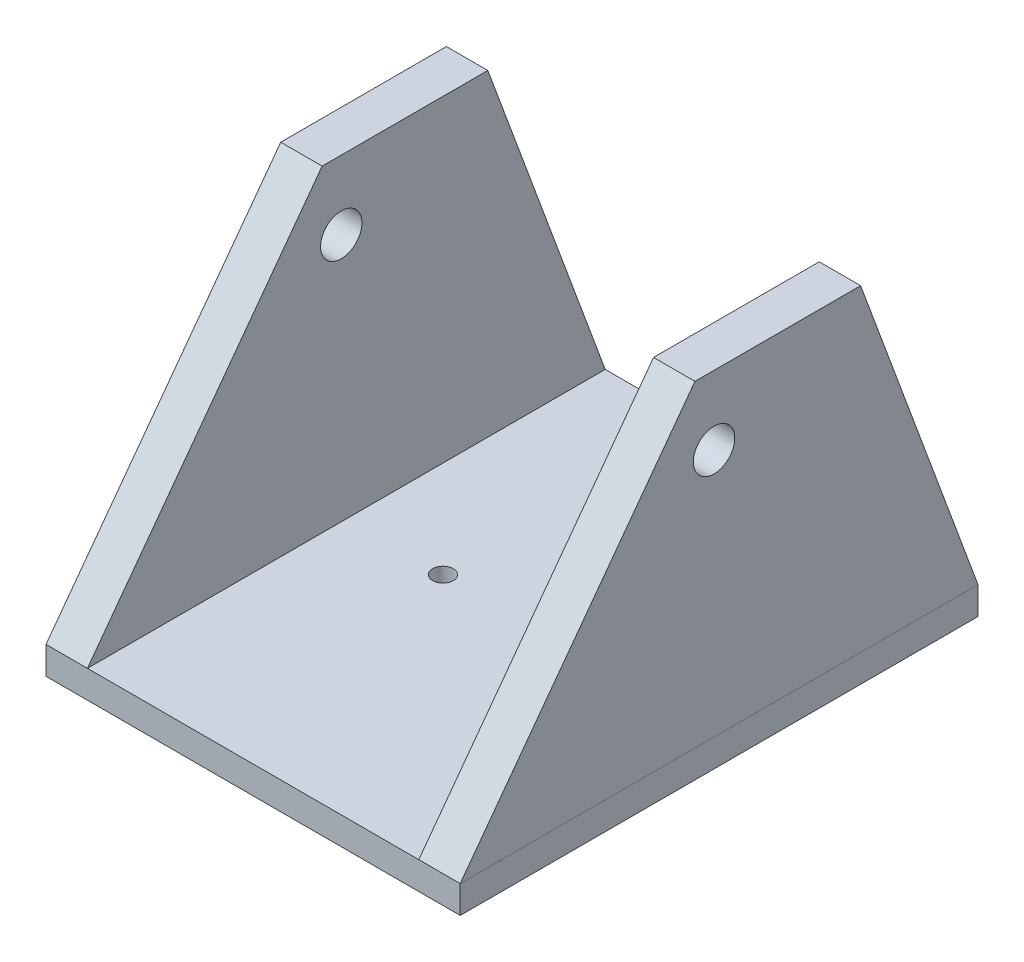
SolidWorks part; units mm, degrees
ref_plane "Front Plane" through (0, 0, 0) normal (0, 0, 1) x (1, 0, 0)
ref_plane "Top Plane" through (0, 0, 0) normal (0, 1, 0) x (1, 0, 0)
ref_plane "Right Plane" through (0, 0, 0) normal (1, 0, 0) x (0, 0, -1)
sketch "Sketch1" plane through (0, 0, 0) normal (0, 1, 0) x (1, 0, 0)
  line L0 (30, 0) -> (-30, 0)
  line L1 (-30, 0) -> (-30, 75)
  line L2 (-30, 75) -> (30, 75)
  line L3 (0, 0) -> (0, 87.606) construction
  line L4 (30, 0) -> (30, 75)
  point P9 (0, 75)
extrude "Boss-Extrude1" add sketch "Sketch1" along normal blind 4
sketch "Sketch2" plane through (0, 4, 0) normal (0, 1, 0) x (1, 0, 0)
  line L0 (-30, 37.5) -> (30, 37.5)
  line L1 (-30, 75) -> (-30, 0) construction
  line L2 (30, 0) -> (30, 75) construction
  line L3 (0, 37.5) -> (10, 37.5)
  line L4 (10, 37.5) -> (-10, 37.5)
  circle A0 centre (-10, 37.5) radius 1.5
  circle A1 centre (10, 37.5) radius 1.5
extrude "Cut-Extrude1" cut sketch "Sketch2" against normal blind 4 and the other way through all contours A0 | A1
sketch "Sketch3" plane through (0, 4, 0) normal (0, 1, 0) x (1, 0, 0)
  line L0 (-30, 75) -> (-24, 75)
  line L1 (30, 75) -> (-30, 75) construction
  line L2 (30, 75) -> (24, 75)
  line L3 (-24, 75) -> (-24, 0)
  line L4 (-30, 0) -> (30, 0) construction
  line L5 (-24, 0) -> (-30, 0)
  line L6 (-30, 0) -> (-30, 75)
  line L7 (24, 75) -> (24, 0)
  line L8 (24, 0) -> (30, 0)
  line L9 (30, 0) -> (30, 75)
  line L10 (-30, 75) -> (-24, 75)
  line L11 (-24, 75) -> (-24, 0)
  line L12 (-24, 0) -> (-30, 0)
  line L13 (-30, 0) -> (-30, 75)
  line L14 (30, 0) -> (30, 75)
  line L15 (-30, 75) -> (-24, 75)
  line L16 (-24, 75) -> (-24, 0)
  line L17 (-24, 0) -> (-30, 0)
  line L18 (-30, 0) -> (-30, 75)
  line L19 (30, 0) -> (30, 75)
  dimension "D1" = 6
  dimension "D2" = 6
ref_plane "Plane1" through (0, 50, 0) normal (0, 1, 0) x (1, 0, 0)
sketch "Sketch4" plane through (0, 50, 0) normal (0, 1, 0) x (1, 0, 0)
  line L0 (-30, 58) -> (-30, 34)
  line L1 (-30, 0) -> (-30, 75) construction
  line L2 (-30, 34) -> (-24, 34)
  line L3 (-24, 75) -> (-24, 0) construction
  line L4 (-24, 34) -> (-24, 58)
  line L5 (-24, 58) -> (-30, 58)
  line L6 (24, 58) -> (24, 34)
  line L8 (24, 34) -> (30, 34)
  line L10 (30, 34) -> (30, 58)
  line L11 (30, 58) -> (24, 58)
  line L12 (-30, 34) -> (-30, 0)
  line L13 (30, 34) -> (30, 0)
  line L14 (30, 0) -> (29.9099, -0.2435)
  point P13 (30, 34)
  dimension "D1" = 34
  dimension "D2" = 24
  dimension "D3" = 34
  dimension "D4" = 24
loft "Loft2" add section "Sketch3" section "Sketch4" connector at (24, 4, 0) connector at (24, 50, -34)
loft "Loft3" add section "Sketch3<11>" section "Sketch4<9>" connector at (-30, 4, 0) connector at (-30, 50, -34)
sketch "Sketch3<11>" plane through (0, 4, 0) normal (0, 1, 0) x (1, 0, 0) same geometry as "Sketch3"
sketch "Sketch4<9>" plane through (0, 50, 0) normal (0, 1, 0) x (1, 0, 0) same geometry as "Sketch4"
ref_plane "Plane2" through (0, 40, 0) normal (0, 1, 0) x (1, 0, 0)
sketch "Sketch5" plane through (0, 40, 0) normal (0, 1, 0) x (1, 0, 0)
  line L0 (42.8778, 36.7666) -> (-35.6291, 36.7666) construction
  point P3 (0, 0)
  point P4 (-35.2749, 36.7666)
  point P5 (42.8778, 36.7666)
sketch "Sketch7" plane through (-30, 0, 0) normal (-1, 0, 0) x (0, 0, 1)
  circle A0 centre (-36.7666, 40) radius 3
extrude "Boss-Extrude2" add sketch "Sketch7" against normal blind 60 contours A0
extrude "Cut-Extrude3" cut sketch "Sketch7<3>" against normal up to vertex (72.8778 mm away) up to point (42.8778, 40, -36.7666)
sketch "Sketch7<3>" plane through (-30, 0, 0) normal (-1, 0, 0) x (0, 0, 1) same geometry as "Sketch7"
